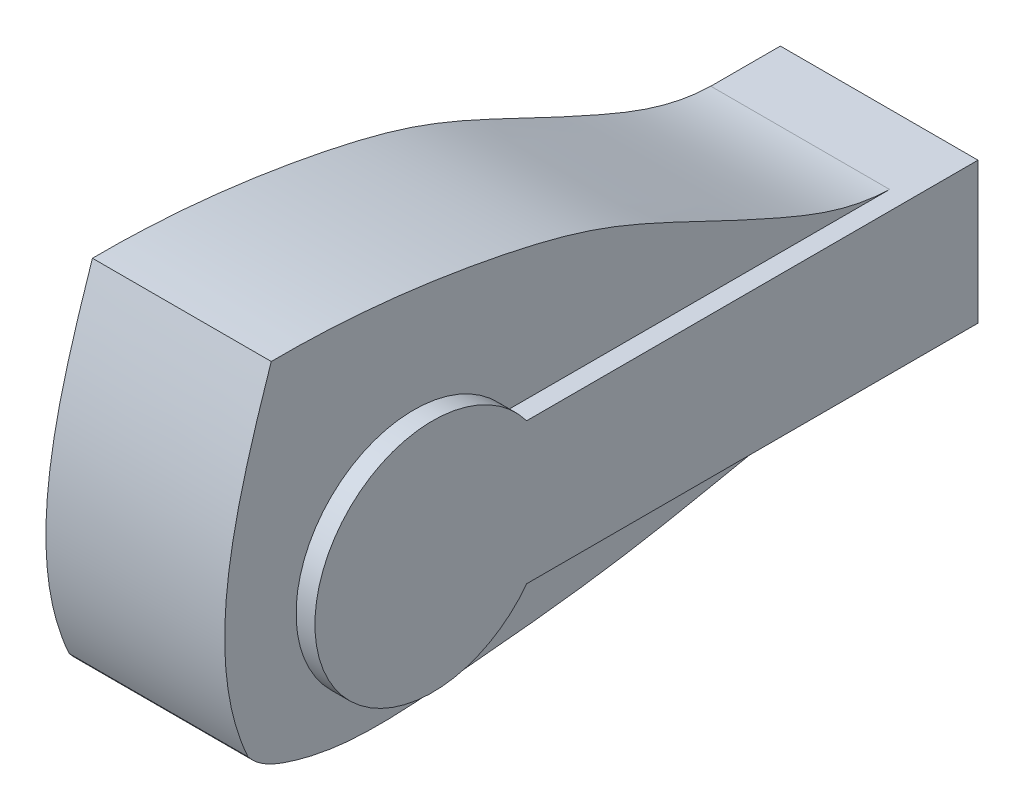
SolidWorks part; units mm, degrees
ref_plane "Front Plane" through (0, 0, 0) normal (0, 0, 1) x (1, 0, 0)
ref_plane "Top Plane" through (0, 0, 0) normal (0, 1, 0) x (1, 0, 0)
ref_plane "Right Plane" through (0, 0, 0) normal (1, 0, 0) x (0, 0, -1)
sketch "Sketch1" plane through (0, 0, 0) normal (1, 0, 0) x (0, 0, -1)
  line L0 (-66.9091, 0) -> (136.6448, 0) construction
  line L1 (-40, 29.9091) -> (-40, -45.5455) construction
  line L2 (110, 29.9091) -> (110, -49.9091) construction
  line L3 (405.0455, -1095.768) -> (919.1218, -1095.768) construction
  line L4 (119.9024, -15) -> (-54.8236, -15) construction
  line L5 (118.703, 15) -> (-47.3601, 15) construction
  dimension "D1" = 40
  dimension "D2" = 150
  dimension "D3" = 15
  dimension "D4" = 15
sketch "Sketch3" plane through (0, 0, 0) normal (1, 0, 0) x (0, 0, -1)
  line L0 (101.1258, 15) -> (115.9037, 15)
  line L1 (115.9037, 15) -> (115.9037, -15)
  line L2 (115.9037, -15) -> (101.1258, -15)
  line L3 (-66.9091, 0) -> (136.6448, 0) construction
  spline S0 degree 3 poles (-30.2788, 49.0428) (-37.7125, 26.8833) (-45.5014, 1.5739) (-35.2285, -21.2287) knots 0 0 0 0 1 1 1 1
  spline S1 degree 3 poles (-35.2285, -21.2287) (-33.0065, -24.0711) (-26.4975, -26.8634) (-11.3353, -30.1292) (12.7191, -27.9297) (43.0967, -25.0576) (73.3871, -18.4311) (92.1269, -14.8672) (101.1258, -15) knots 0 0 0 0 0.075207 0.148741 0.333288 0.588928 0.808106 1 1 1 1
  spline S2 degree 3 poles (-30.2788, 49.0428) (-14.033, 49.1681) (9.2866, 46.5994) (40.5998, 39.0893) (60.0842, 29.5403) (80.2161, 20.13) (93.0556, 15.2371) (101.1258, 15) knots 0 0 0 0 0.354357 0.512751 0.701526 0.826928 1 1 1 1
  point P7 (100.7475, -14.8354)
  dimension "D1" = 15
  dimension "D2" = 15
extrude "Boss-Extrude1" add sketch "Sketch3" along normal blind 19 and the other way blind 19
sketch "Sketch4" plane through (19, 0, 0) normal (1, 0, 0) x (0, 0, -1)
  circle A0 centre (0, 0) radius 25
  dimension "D1" = 50
extrude "Boss-Extrude2" add sketch "Sketch4" along normal blind 4
sketch "Sketch7" plane through (19, 0, 0) normal (1, 0, 0) x (0, 0, -1)
  line L0 (119.9024, -15) -> (-54.8236, -15) construction
  line L1 (115.9037, 15) -> (19.5688, 15)
  line L2 (115.9037, 15) -> (115.9037, -15)
  line L3 (115.9037, -15) -> (19.5688, -15)
  line L4 (19.5688, 15) -> (19.5688, -15)
extrude "Boss-Extrude4" add sketch "Sketch7" along normal blind 4
sketch "Sketch8" plane through (0, 0, -115.9037) normal (0, 0, -1) x (-1, 0, 0)
  line L1 (0, 15) -> (-23, 15)
  line L2 (0, 15) -> (0, -15)
  line L3 (0, -15) -> (-23, -15)
  line L4 (-23, 15) -> (-23, -15)
  circle A0 centre (0, 0) radius 15
  dimension "D1" = 30
ref_plane "Plane1" through (0, 15, 0) normal (0, 1, 0) x (1, 0, 0)
ref_plane "Plane2" through (0, -15, 0) normal (0, 1, 0) x (1, 0, 0)
sketch "Sketch13" plane through (0, 15, 0) normal (0, 1, 0) x (1, 0, 0)
  line L0 (25.7274, 20) -> (23, 20)
  line L1 (19, 101.1258) -> (19, 135.4629) construction
  line L2 (0, 115.9037) -> (23, 115.9037) construction
  line L3 (25.7274, 20) -> (25.7274, 115.9037)
  line L4 (25.7274, 115.9037) -> (19, 115.9037)
  spline S0 degree 2 poles (19, 115.9037) (20.4724, 67.9291) (23, 20) knots 0 0 0 1 1 1
